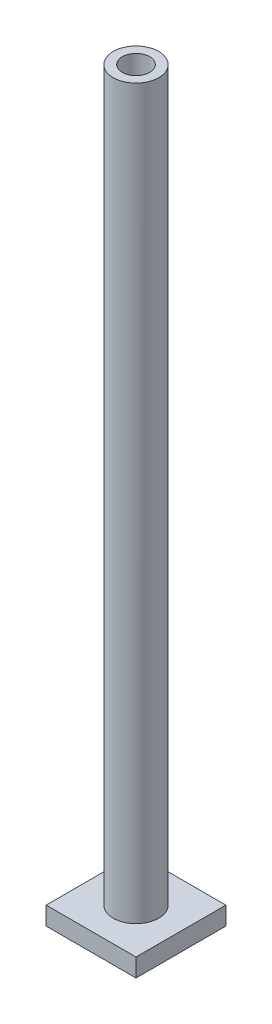
SolidWorks part; units mm, degrees
ref_plane "Front Plane" through (0, 0, 0) normal (0, 0, 1) x (1, 0, 0)
ref_plane "Top Plane" through (0, 0, 0) normal (0, 1, 0) x (1, 0, 0)
ref_plane "Right Plane" through (0, 0, 0) normal (1, 0, 0) x (0, 0, -1)
sketch "Sketch1" plane through (0, 0, 0) normal (0, 1, 0) x (1, 0, 0)
  line L1 (7.9, 7.9) -> (-7.9, 7.9)
  line L2 (7.9, 7.9) -> (7.9, -7.9)
  line L3 (7.9, -7.9) -> (-7.9, -7.9)
  line L4 (-7.9, 7.9) -> (-7.9, -7.9)
  line L5 (7.9, 7.9) -> (-7.9, -7.9) construction
  line L6 (7.9, -7.9) -> (-7.9, 7.9) construction
  point P0 (0, 0)
  dimension "D1" = 15.8
extrude "Base" add sketch "Sketch1" along normal blind 3.2
sketch "Sketch2" plane through (0, 0, 0) normal (0, -1, 0) x (1, 0, 0)
  line L0 (0, 6.7) -> (0, -6.7) construction
  line L1 (6.7, 6.7) -> (-6.7, 6.7)
  line L2 (6.7, 6.7) -> (6.7, -6.7)
  line L3 (6.7, -6.7) -> (-6.7, -6.7)
  line L4 (-6.7, 6.7) -> (-6.7, -6.7)
  line L5 (6.7, 6.7) -> (-6.7, -6.7) construction
  line L6 (6.7, -6.7) -> (-6.7, 6.7) construction
  line L7 (-6.7, 0) -> (6.7, 0) construction
  line L8 (-7.9, -7.9) -> (-7.9, 7.9) construction
  circle A4 centre (0, 0) radius 3.3
  circle A5 centre (0, 0) radius 2.5
  point P0 (0, 0)
  dimension "D4" = 5
  dimension "D2" = 1.2
  dimension "D5" = 0.8
extrude "Bottom cut" cut sketch "Sketch2" against normal offset from surface (2 mm away) 1.2 contours L1 L4 L3 L2 A4 | A5 region at (6.5105, 0, 0) region at (0, 0, 0) up to face at (0, 3.2, 0)
sketch "Sketch3" plane through (0, 3.2, 0) normal (0, 1, 0) x (1, 0, 0)
  circle A0 centre (0, 0) radius 4
  circle A1 centre (0, 0) radius 2.4
  dimension "D1" = 8
  dimension "D2" = 1.6
extrude "Lamp post" add sketch "Sketch3" along normal blind 128
sketch "Sketch4" plane through (0, 3.2, 0) normal (0, 1, 0) x (1, 0, 0)
  circle A0 centre (0, 0) radius 2.4 construction
  circle A1 centre (0, 0) radius 2.4
extrude "Wire bottom cut" cut sketch "Sketch4" against normal up to next
equation "\"P\"= \"LegoUnit\" * 5"
equation "\"D1@Sketch1\" = \"BrickSize\" * 2 - \"Padding\""
equation "\"Padding\"= \"LegoUnit\" / 8"
equation "\"SmallHeight\"= \"LegoUnit\" * 2"
equation "\"LargeHight\"= \"LegoUnit\" * 6"
equation "\"D1@Base\" = \"SmallHeight\""
equation "\"InsetDiameter\"= \"LegoUnit\" * 2 - \"Padding\" * 3"
equation "\"LegoUnit\"=1.6"
equation "\"BrickSize\"= \"LegoUnit\" * 5"
equation "\"WallSize\"= \"LegoUnit\" - \"Padding\" * 2"
equation "\"D2@Sketch2\"=\"WallSize\""
equation "\"BumpSize\"= \"LegoUnit\" * 3"
equation "\"InsideBumpSize\"= \"BumpSize\" + \"Padding\""
equation "\"InnerWallSize\"= \"Padding\" * 4"
equation "\"D5@Sketch2\"=\"InnerWallSize\""
equation "\"CeilingSize\"= \"LegoUnit\" - \"Padding\" * 2"
equation "\"D1@Bottom cut\" = \"CeilingSize\""
equation "\"D4@Sketch2\"=\"InsideBumpSize\""
equation "\"D1@Sketch3\"=\"BrickSize\""
equation "\"D2@Sketch3\"=\"LegoUnit\""
equation "\"D1@Lamp post\"=\"SmallHeight\" * 40"
